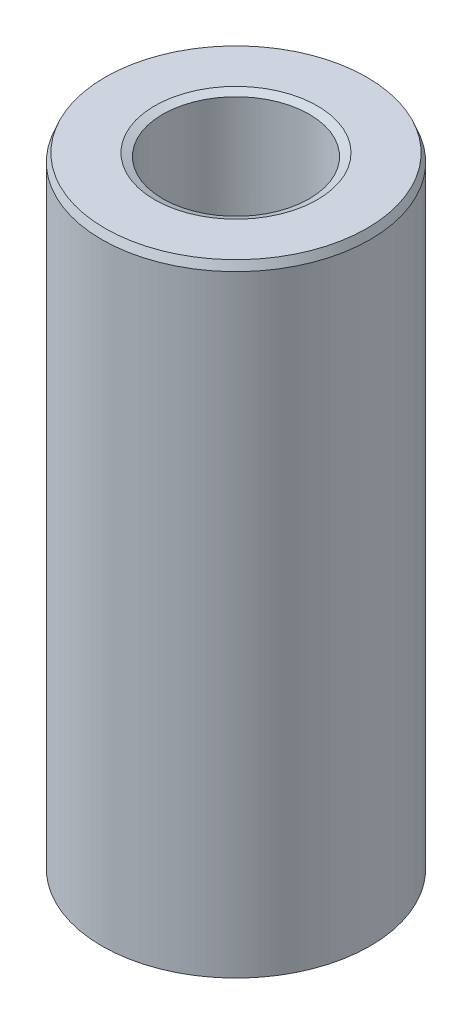
SolidWorks part; units mm, degrees
ref_plane "Front Plane" through (0, 0, 0) normal (0, 0, 1) x (1, 0, 0)
ref_plane "Top Plane" through (0, 0, 0) normal (0, 1, 0) x (1, 0, 0)
ref_plane "Right Plane" through (0, 0, 0) normal (1, 0, 0) x (0, 0, -1)
sketch "Sketch1" plane through (0, 0, 0) normal (0, 1, 0) x (1, 0, 0)
  circle A0 centre (0, 0) radius 12.5
  dimension "SLEEVE_OD" = 25
extrude "Boss-Extrude1" add sketch "Sketch1" along normal blind 58.061
sketch "Sketch2" plane through (0, 0, 0) normal (0, 1, 0) x (1, 0, 0)
  circle A0 centre (0, 0) radius 6.8258
  dimension "BORE_D" = 13.6516
extrude "Cut-Extrude1" cut sketch "Sketch2" along normal through all
chamfer "Chamfer1" distance 0.7552 angle 21.717 4 edges at (0, 58.061, 6.8258) (0, 0, 6.8258) (0, 0, 12.5) (0, 58.061, 12.5) first distance on face at (0, 58.061, 6.8258) first distance on face at (0, 0, 6.8258) first distance on face at (0, 58.061, 12.5)
